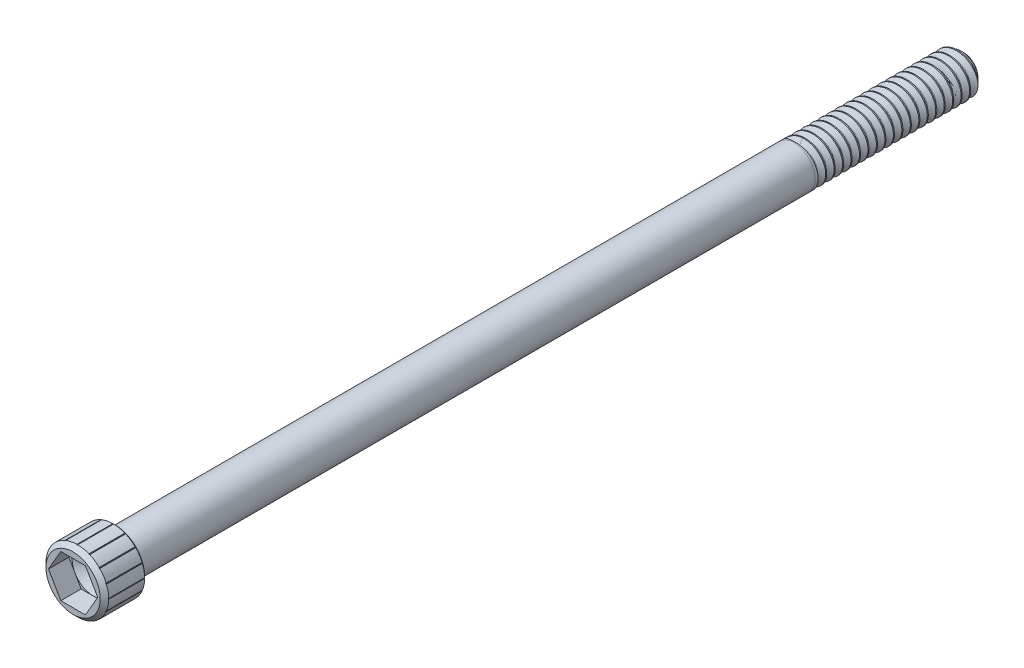
SolidWorks part; units mm, degrees
material "Alloy Steel (SS)"
ref_plane "Front Plane" through (0, 0, 0) normal (0, 0, 1) x (1, 0, 0)
ref_plane "Top Plane" through (0, 0, 0) normal (0, 1, 0) x (1, 0, 0)
ref_plane "Right Plane" through (0, 0, 0) normal (1, 0, 0) x (0, 0, -1)
sketch "Sketch1" plane through (0, 0, 0) normal (1, 0, 0) x (0, 0, -1)
  line L0 (4.8921, 0) -> (133.4516, 0)
  line L1 (0, 3.194) -> (0, 4.064)
  line L2 (6.2738, 3.3115) -> (6.2738, 4.445)
  line L3 (0.635, 4.699) -> (6.0198, 4.699)
  line L4 (-1000, 4.699) -> (49000, 4.699) construction
  line L5 (-1000, 0) -> (49000, 0) construction
  line L6 (133.4516, 0) -> (133.4516, 2.159)
  line L7 (0, -1000) -> (0, 49000) construction
  line L8 (6.2738, -1000) -> (6.2738, 49000) construction
  line L9 (133.4516, -1000) -> (133.4516, 49000) construction
  line L10 (0, 4.064) -> (0.635, 4.699)
  line L11 (6.2738, 4.445) -> (6.0198, 4.699)
  line L12 (0, 3.194) -> (3.048, 3.194)
  line L13 (0, 3.194) -> (133.4516, 3.194) construction
  line L14 (0, 0) -> (133.4516, 0) construction
  line L15 (114.4016, 3.1236) -> (132.487, 3.1236)
  line L16 (3.048, 3.194) -> (4.8921, 0)
  line L17 (4.8921, 3.1236) -> (133.4516, 3.1236) construction
  line L19 (108.0516, 3.1337) -> (114.4016, 3.1236)
  line L21 (132.487, 3.1236) -> (133.4516, 2.159)
  line L22 (6.4516, 3.1337) -> (108.0516, 3.1337)
  line L23 (4.8921, 3.1337) -> (133.4516, 3.1337) construction
  arc A0 (6.2738, 3.3115) -> (6.4516, 3.1337) centre (6.4516, 3.3115) ccw
  point P9 (0, 4.699)
  point P13 (6.2738, 4.699)
  dimension "D11" = 0.1778
  dimension "D1" = 6.2738
  dimension "D2" = 4.699
  dimension "D3" = 45
  dimension "D4" = 45
  dimension "D6" = 3.194
  dimension "D8" = 30
  dimension "D9" = 3.048
  dimension "D10" = 3.1337
  dimension "D12" = 6.35
  dimension "D13" = 19.05
  dimension "D14" = 45
  dimension "D15" = 3.1236
  dimension "D16" = 0.9646
  dimension "D17" = 0.092
  dimension "D7" = 0.254
revolve "Revolve1" add sketch "Sketch1" angle 360 about L0
sketch "Sketch2" plane through (0, 0, 0) normal (0, 0, 1) x (1, 0, 0)
  line L0 (-1.8441, 3.194) -> (1.8441, 3.194)
  line L1 (1.8441, 3.194) -> (3.6882, 0)
  line L2 (3.6882, 0) -> (1.8441, -3.194)
  line L3 (1.8441, -3.194) -> (-1.8441, -3.194)
  line L4 (-1.8441, -3.194) -> (-3.6882, 0)
  line L5 (-3.6882, 0) -> (-1.8441, 3.194)
  point P14 (0, 0)
  dimension "D2" = 6.3881
  dimension "D3" = 7.3763
  dimension "D1" = 6
extrude "Cut-Extrude1" cut sketch "Sketch2" against normal blind 3.048
sketch "Sketch3" plane through (0, 0, -133.4516) normal (0, 0, -1) x (-1, 0, 0)
  circle A0 centre (0, 0) radius 3.1337
  circle A1 centre (0, 0) radius 2.159 construction
  dimension "D1" = 6.2674
curve "Helix/Spiral1" pitch 1.27 height 25.4 turns 20
sketch "Sketch4" plane through (0, 0, 0) normal (1, 0, 0) x (0, 0, -1)
  line L0 (133.4516, 3.1214) -> (133.6104, 3.1214) construction
  line L1 (134.2848, 2.3647) -> (134.166, 2.159) construction
  line L2 (133.4516, 3.1214) -> (133.531, 3.2589) construction
  line L3 (134.0072, 2.434) -> (134.3247, 2.434) construction
  line L4 (133.531, 3.2589) -> (133.6104, 3.1214) construction
  line L5 (134.166, 2.159) -> (134.0472, 2.3647) construction
  line L6 (133.5896, 3.1572) -> (134.0472, 2.3647)
  line L7 (134.2848, 2.3647) -> (134.7423, 3.1572)
  line L8 (133.5896, 3.1572) -> (134.7423, 3.1572)
  line L9 (133.4516, 2.159) -> (133.4516, -2.1612) construction
  arc A0 (134.0472, 2.3647) -> (134.2848, 2.3647) centre (134.166, 2.4333) ccw
  dimension "D9" = 0.1372
  dimension "D2" = 1.0999
  dimension "D5" = 0.275
  dimension "D6" = 1.1527
  dimension "D10" = 0.7233
  dimension "D11" = 0.0692
  dimension "D13" = 0.1587
  dimension "D3" = 0.1375
  dimension "D4" = 0.3175
  dimension "D8" = 60
sweep "Cut-Sweep1" cut profiles "Sketch4" path "Helix/Spiral1"
sketch "Sketch5" plane through (0, 0, 0) normal (1, 0, 0) x (0, 0, -1)
  line L3 (108.2034, 3.1335) -> (108.6472, 2.3647)
  line L4 (108.8848, 2.3647) -> (109.3276, 3.1317)
  line L5 (109.3276, 3.1317) -> (108.2034, 3.1335)
  line L6 (108.2034, 3.1335) -> (108.6472, 2.3647)
  line L7 (108.8848, 2.3647) -> (109.3276, 3.1317)
  line L8 (109.3276, 3.1317) -> (108.2034, 3.1335)
  arc A1 (108.6472, 2.3647) -> (108.8848, 2.3647) centre (108.766, 2.4333) ccw
  arc A2 (108.6472, 2.3647) -> (108.8848, 2.3647) centre (108.766, 2.4333) ccw
  dimension "D1" = 0
extrude "Cut-Extrude2" cut sketch "Sketch5" against normal through all
sketch "Sketch6" plane through (0, 0, 0) normal (0, 0, 1) x (1, 0, 0)
  line L0 (0, 3.194) -> (0, 0) construction
  line L1 (0.018, 4.6535) -> (0.0631, 4.6986)
  line L2 (-0.0631, 4.6986) -> (-0.018, 4.6535)
  line L3 (1.8441, 3.194) -> (-1.8441, 3.194) construction
  arc A0 (0.018, 4.6535) -> (-0.018, 4.6535) centre (0, 4.6714) cw
  arc A3 (0.0631, 4.6986) -> (-0.0631, 4.6986) centre (0, 0) ccw
  point P11 (0, 4.6355)
  dimension "D1" = 4.699
  dimension "D3" = 0.0254
  dimension "D2" = 0.0631
extrude "Cut-Extrude3" cut sketch "Sketch6" against normal up to next
pattern_circular "CirPattern1" count 16 over 360 about axis through (0, 0, 0) along (0, 0, 1) of "Cut-Extrude3"
equation "\"P\"= .05in"
equation "\"H\"= \"P\" * cos ( 30deg )"
equation "\"D13@Sketch4\" = .125 * \"P\""
equation "\"D2@Sketch4\" = \"H\""
equation "\"D3@Sketch4\" = .125 * \"H\""
equation "\"D5@Sketch4\" = .25 * \"H\""
equation "\"D4@Sketch4\" = .25 * \"P\""
equation "\"D9@Sketch4\" = .108 * \"P\""
